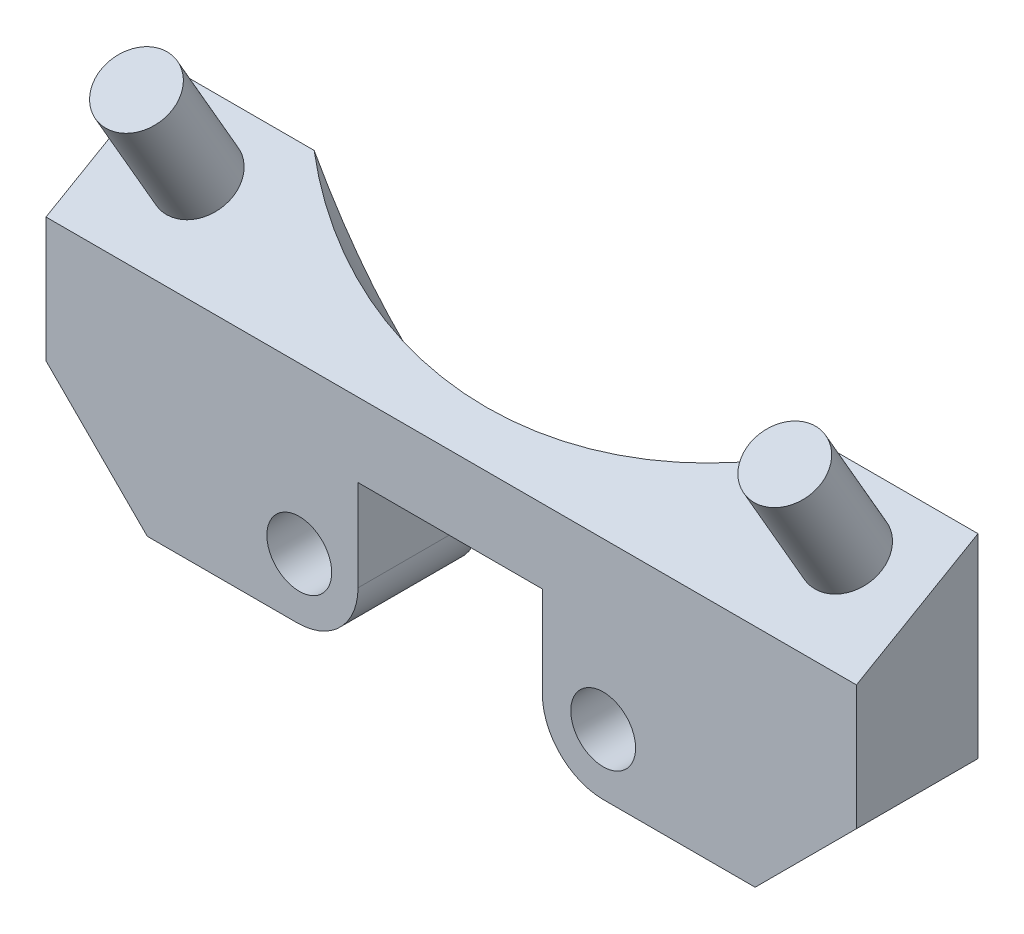
SolidWorks part; units mm, degrees
ref_plane "Front Plane" through (0, 0, 0) normal (0, 0, 1) x (1, 0, 0)
ref_plane "Top Plane" through (0, 0, 0) normal (0, 1, 0) x (1, 0, 0)
ref_plane "Right Plane" through (0, 0, 0) normal (1, 0, 0) x (0, 0, -1)
ref_plane "Plane1" [suppressed] through (-82, -11.15, 0) normal (0, 0, -1) x (-1, 0, 0)
sketch "Sketch3" plane through (0, 0, 0) normal (0, 0, 1) x (1, 0, 0)
  line L0 (-42, 0) -> (-42, -11.15)
  line L1 (-69.5, -8.15) -> (-54.5, -8.15) construction
  line L2 (-62, -11.15) -> (-62, -8.15) construction
  line L3 (-66.6, -3.65) -> (-66.6, -11.15)
  line L4 (-57.5, -3.65) -> (-57.5, -11.15)
  line L5 (-57.5, -11.15) -> (-42, -11.15)
  line L6 (-66.6, -3.65) -> (-57.5, -3.65)
  line L49 (-42, 0) -> (-82, 0)
  line L50 (-82, 0) -> (-82, -11.15)
  line L51 (-82, -11.15) -> (-66.6, -11.15)
  circle A0 centre (-69.5, -8.15) radius 1.6
  circle A1 centre (-54.5, -8.15) radius 1.6
  arc A2 (-57.5, -8.15) -> (-66.5, -8.15) centre (-62, -8.15) ccw construction
  dimension "D2" = 3.2
  dimension "D6" = 9
  dimension "D3" = 40
  dimension "D4" = 3
  dimension "D1" = 11.15
  dimension "D5" = 15
extrude "Boss-Extrude1" add sketch "Sketch3" along normal blind 6 contours L0 L5 L4 L6 L3 L51 L50 L49 | A1 | A0
sketch "Sketch4" plane through (0, 0, 6) normal (0, 0, 1) x (1, 0, 0)
  line L0 (-42, 0) -> (-82, 0) construction
  line L1 (-71.1, -5.3787) -> (-72.7, -8.15) construction
  line L2 (-72.7, -8.15) -> (-71.1, -10.9213) construction
  line L3 (-71.1, -10.9213) -> (-67.9, -10.9213) construction
  line L4 (-67.9, -10.9213) -> (-66.3, -8.15) construction
  line L5 (-66.3, -8.15) -> (-67.9, -5.3787) construction
  line L6 (-67.9, -5.3787) -> (-71.1, -5.3787) construction
  line L7 (-56.1, -5.3787) -> (-57.7, -8.15) construction
  line L8 (-57.7, -8.15) -> (-56.1, -10.9213) construction
  line L9 (-56.1, -10.9213) -> (-52.9, -10.9213) construction
  line L10 (-52.9, -10.9213) -> (-51.3, -8.15) construction
  line L11 (-51.3, -8.15) -> (-52.9, -5.3787) construction
  line L12 (-52.9, -5.3787) -> (-56.1, -5.3787) construction
  line L13 (-82, 0) -> (-82, -11.15) construction
  line L16 (-42, 0) -> (-82, 0)
  line L17 (-82, 0) -> (-82, -11.15)
  line L18 (-82, -11.15) -> (-42, -11.15)
  line L19 (-42, 0) -> (-42, -11.15)
  line L20 (-57.5, -11.15) -> (-42, -11.15) construction
  circle A0 centre (-69.5, -8.15) radius 3.2 construction
  circle A1 centre (-54.5, -8.15) radius 3.2 construction
  dimension "D1" = 6.4
  dimension "D2" = 6.4
extrude "Boss-Extrude2" [suppressed] add sketch "Sketch4" along normal blind 2.5
sketch "Sketch5" plane through (-82, 0, 0) normal (-1, 0, 0) x (0, 0, 1)
  line L0 (0, 0) -> (0, 3.4641)
  line L1 (0, 3.4641) -> (6, 0)
  line L6 (6, 0) -> (0, 0)
  dimension "D1" = 30
extrude "Boss-Extrude3" add sketch "Sketch5" against normal up to surface (40 mm away) up to face at (-42, -5.575, 3)
ref_plane "Plane2" through (-62, 0, 0) normal (1, 0, 0) x (0, 0, -1)
sketch "Sketch7" plane through (0, 4.1891, -1.2557) normal (0, 0.866, 0.5) x (-1, 0, 0)
  line L0 (42, 8.3781) -> (82, 8.3781) construction
  circle A0 centre (78, 4.3781) radius 1.75
  dimension "D1" = 3.5
  dimension "D2" = 4
  dimension "D3" = 4
extrude "Boss-Extrude5" add sketch "Sketch7" along normal blind 6
mirror "Mirror2" about plane through (-62, 0, 0) normal (1, 0, 0) of "Boss-Extrude5"
sketch "Sketch8" plane through (0, 0, 6) normal (0, 0, 1) x (1, 0, 0)
  line L6 (-42, 0) -> (-82, 0)
  line L7 (-42, 0) -> (-82, 0)
  line L8 (-82, 0) -> (-82, -11.15)
  line L9 (-82, 0) -> (-82, -11.15)
  line L10 (-82, -11.15) -> (-66.6, -11.15)
  line L11 (-82, -11.15) -> (-66.6, -11.15)
  line L12 (-66.6, -11.15) -> (-66.6, -3.65)
  line L13 (-66.6, -11.15) -> (-66.6, -3.65)
  line L14 (-57.5, -3.65) -> (-57.5, -11.15)
  line L15 (-57.5, -3.65) -> (-57.5, -11.15)
  line L16 (-57.5, -11.15) -> (-42, -11.15)
  line L17 (-57.5, -11.15) -> (-42, -11.15)
  line L19 (-42, -11.15) -> (-42, 0)
  line L20 (-42, -11.15) -> (-42, 0)
  line L22 (-66.6, -3.65) -> (-57.5, -3.65)
  line L23 (-66.6, -3.65) -> (-57.5, -3.65)
  circle A0 centre (-54.5, -8.15) radius 1.6 construction
  circle A1 centre (-54.5, -8.15) radius 1.6
  circle A2 centre (-69.5, -8.15) radius 1.6 construction
  circle A3 centre (-69.5, -8.15) radius 1.6
  dimension "D1" = 0
extrude "Boss-Extrude6" [suppressed] add sketch "Sketch8" against normal blind 0.5 contours A1
chamfer "Chamfer1" distance 5 angle 45 2 edges at (-82, -11.15, 3) (-42, -11.15, 3)
fillet "Fillet1" radius 3 2 edges at (-57.5, -11.15, 3) (-66.6, -11.15, 3)
sketch "Sketch9" plane through (0, 2.5981, 1.5) normal (0, 0.866, 0.5) x (1, 0, 0)
  line L0 (-62, 1.7321) -> (-62, 15.8038) construction
  line L1 (-42, 1.7321) -> (-82, 1.7321) construction
  line L2 (-62, -3.3) -> (-62, 3.3) construction
  circle A0 centre (-62, 15.8038) radius 19
  circle A1 centre (-78, -1.1962) radius 1.75 construction
  dimension "D1" = 38
  dimension "D2" = 17
extrude "Cut-Extrude1" cut sketch "Sketch9" against normal through all
